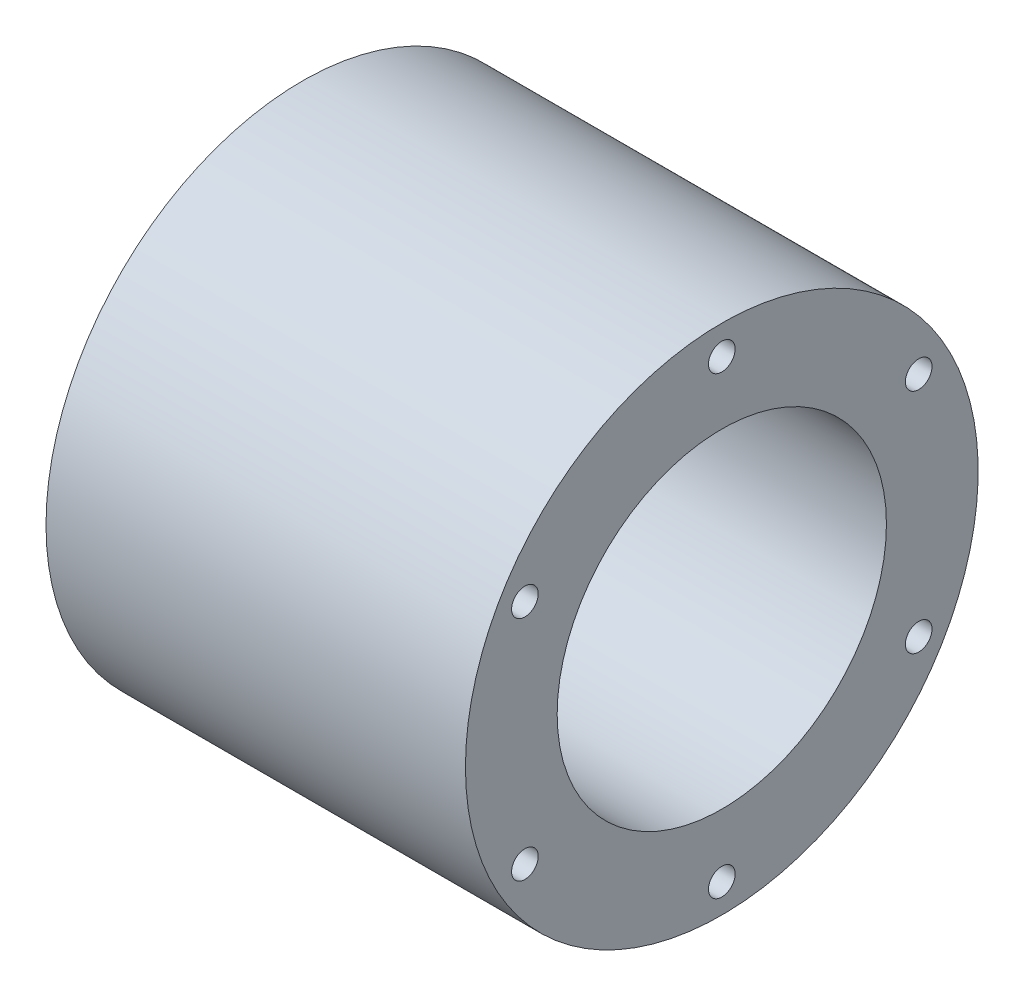
SolidWorks part; units mm, degrees
material "7075-O (SS)"
ref_plane "Front" through (0, 0, 0) normal (0, 0, 1) x (1, 0, 0)
ref_plane "Top" through (0, 0, 0) normal (0, 1, 0) x (1, 0, 0)
ref_plane "Right" through (0, 0, 0) normal (1, 0, 0) x (0, 0, -1)
sketch "Croquis1" plane through (0, 0, 0) normal (1, 0, 0) x (0, 0, -1)
  circle A0 centre (0, 0) radius 21
  circle A1 centre (0, 0) radius 32.7
  dimension "D1" = 42
  dimension "D2" = 65.4
extrude "Saliente-Extruir1" add sketch "Croquis1" along normal mid plane 48.5
sketch "Croquis3" plane through (-24.25, 0, 0) normal (-1, 0, 0) x (0, 0, 1)
  line L6 (-18, -21) -> (18, -21)
  line L15 (-21, -18) -> (-21, 18)
  line L16 (-18, 21) -> (18, 21)
  line L17 (21, -18) -> (21, 18)
  line L18 (-21, -21) -> (21, 21) construction
  line L19 (-21, 21) -> (21, -21) construction
  circle A0 centre (0, 0) radius 32.7 construction
  circle A1 centre (0, 0) radius 32.7
  arc A2 (-18, -21) -> (-21, -18) centre (-18, -18) cw
  arc A3 (18, -21) -> (21, -18) centre (18, -18) ccw
  arc A4 (18, 21) -> (21, 18) centre (18, 18) cw
  arc A5 (-21, 18) -> (-18, 21) centre (-18, 18) cw
  dimension "D2" = 3
  dimension "D1" = 42
extrude "Saliente-Extruir3" add sketch "Croquis3" along normal blind 5
sketch "Croquis4" plane through (-24.25, 0, 0) normal (-1, 0, 0) x (0, 0, 1)
  line L1 (-15.5, -15.5) -> (15.5, -15.5) construction
  line L2 (-15.5, -15.5) -> (-15.5, 15.5) construction
  line L3 (-15.5, 15.5) -> (15.5, 15.5) construction
  line L4 (15.5, -15.5) -> (15.5, 15.5) construction
  line L5 (-15.5, -15.5) -> (15.5, 15.5) construction
  line L6 (-15.5, 15.5) -> (15.5, -15.5) construction
  circle A0 centre (15.5, 15.5) radius 3.5
  circle A1 centre (-15.5, 15.5) radius 3.5
  circle A2 centre (-15.5, -15.5) radius 3.5
  circle A3 centre (15.5, -15.5) radius 3.5
  point P0 (0, 0)
  dimension "D2" = 7
  dimension "D1" = 31
extrude "Cortar-Extruir1" cut sketch "Croquis4" against normal blind 6
hole_wizard "Taladro de margen para M31" positions "Croquis5" profile "Croquis7" hole size "M3" standard "Ansi Metric"
sketch "Croquis5" plane through (24.25, 0, 0) normal (1, 0, 0) x (0, 0, -1)
  line L0 (0, 29.425) -> (0, -29.425) construction
  line L1 (29.425, 0) -> (-29.425, 0) construction
  point P0 (0, 29)
  point P12 (25.1147, 14.5)
  point P13 (25.1147, -14.5)
  point P14 (0, -29)
  point P15 (-25.1147, -14.5)
  point P16 (-25.1147, 14.5)
  point P18 (0, -28.0309)
  dimension "D1" = 29
  dimension "D3" = 29
  dimension "D2" = 6
sketch "Croquis7" plane through (24.25, 29, 0) normal (0, 1, 0) x (0, 0, -1)
  line L0 (0, 0) -> (0, 11.0215)
  line L1 (0, 11.0215) -> (1.7, 10)
  line L2 (1.7, 10) -> (1.7, 0)
  line L5 (1.7, 0) -> (0, 0)
  line L10 (0, 11.0215) -> (-1.7, 10) construction
  line L11 (0, -6.35) -> (0, 107.95) construction
  dimension "Diámetro de taladro" = 3.4
  dimension "Profundidad de taladro" = 10
  dimension "Ángulo de perforador" = 118
